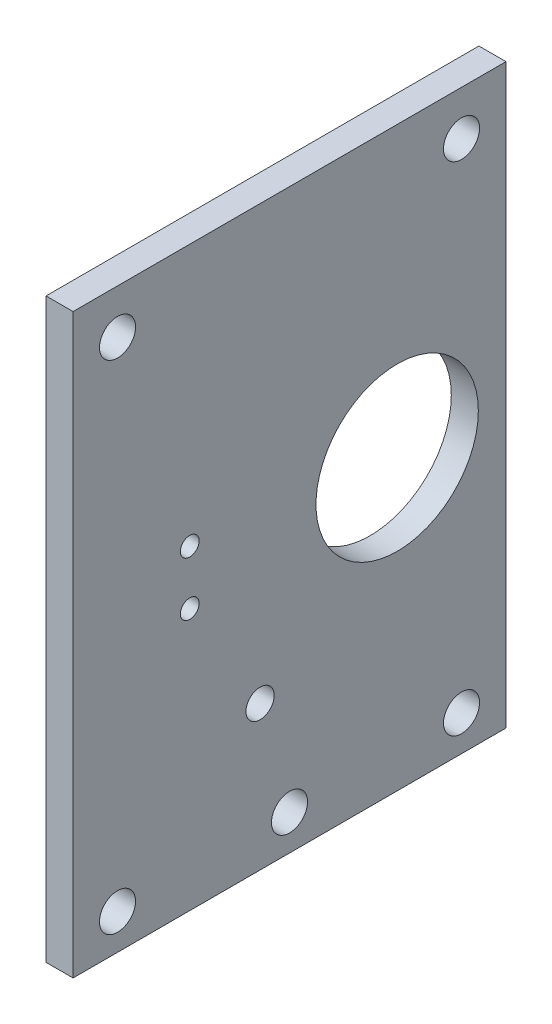
SolidWorks part; units mm, degrees
material "6061 Alloy"
ref_plane "Front Plane" through (0, 0, 0) normal (0, 0, 1) x (1, 0, 0)
ref_plane "Top Plane" through (0, 0, 0) normal (0, 1, 0) x (1, 0, 0)
ref_plane "Right Plane" through (0, 0, 0) normal (1, 0, 0) x (0, 0, -1)
sketch "Sketch2" plane through (0, 0, 0) normal (1, 0, 0) x (0, 0, -1)
  line L1 (-38.1, -50.8) -> (38.1, -50.8)
  line L2 (-38.1, -50.8) -> (-38.1, 50.8)
  line L3 (-38.1, 50.8) -> (38.1, 50.8)
  line L4 (38.1, -50.8) -> (38.1, 50.8)
  line L5 (-38.1, -50.8) -> (38.1, 50.8) construction
  line L6 (-38.1, 50.8) -> (38.1, -50.8) construction
  point P0 (0, 0)
  dimension "D1" = 76.2
  dimension "D2" = 101.6
extrude "Boss-Extrude1" add sketch "Sketch2" along normal blind 4.7625
sketch "Sketch3" plane through (4.7625, 0, 0) normal (1, 0, 0) x (0, 0, -1)
  line L5 (30.2768, -44.5643) -> (-30.2768, -44.5643) construction
  line L6 (-30.2768, 42.9768) -> (30.2768, 42.9768) construction
  line L7 (30.2768, 42.9768) -> (30.2768, -44.5643) construction
  line L8 (-30.2768, 42.9768) -> (-30.2768, -44.5643) construction
  line L9 (-38.1, 50.8) -> (-38.1, -50.8) construction
  line L10 (38.1, 50.8) -> (-38.1, 50.8) construction
  line L11 (38.1, -50.8) -> (38.1, 50.8) construction
  line L12 (-38.1, -50.8) -> (38.1, -50.8) construction
  circle A0 centre (30.2768, -44.5643) radius 3.175
  circle A1 centre (30.2768, 42.9768) radius 3.175
  circle A2 centre (-30.2768, 42.9768) radius 3.175
  circle A3 centre (-30.2768, -44.5643) radius 3.175
  circle A4 centre (18.9484, 0) radius 14.2875
  circle A5 centre (-5.1816, -25.4) radius 2.4892
  circle A6 centre (0, -44.5643) radius 3.175
  dimension "D1" = 6.35
  dimension "D5" = 7.8232
  dimension "D7" = 7.8232
  dimension "D8" = 6.2357
  dimension "D9" = 28.575
  dimension "D10" = 50.8
  dimension "D11" = 4.9784
  dimension "D12" = 25.4
  dimension "D6" = 7.8232
  dimension "D13" = 24.13
  dimension "D14" = 19.1516
extrude "Cut-Extrude1" cut sketch "Sketch3" against normal blind 6.35 contours A1
extrude "Cut-Extrude2" cut sketch "Sketch3<4>" against normal blind 6.35
sketch "Sketch3<4>" plane through (4.7625, 0, 0) normal (1, 0, 0) x (0, 0, -1) same geometry as "Sketch3"
hole_wizard "M6 Clearance Hole1" positions "Sketch5" profile "Sketch4" hole size "M4x0.7" standard "ANSI Metric" end condition up to next
sketch "Sketch5" plane through (4.7625, 0, 0) normal (1, 0, 0) x (0, 0, -1)
  circle A0 centre (-17.5641, 4.7625) radius 1.65 construction
  circle A1 centre (-17.5641, -4.7625) radius 1.65 construction
  point P0 (-17.5641, -4.7625)
  point P2 (-17.5641, 4.7625)
sketch "Sketch4" plane through (4.7625, -4.7625, 17.5641) normal (0, 1, 0) x (0, 0, -1)
  line L0 (0, 0) -> (0, 4.7625)
  line L1 (0, 4.7625) -> (1.65, 4.7625)
  line L2 (1.65, 4.7625) -> (1.65, 0)
  line L5 (1.65, 0) -> (0, 0)
  line L11 (0, -6.35) -> (0, 107.95) construction
  dimension "Thru Hole Dia." = 3.3
  dimension "Thru Hole Depth" = 4.7625
